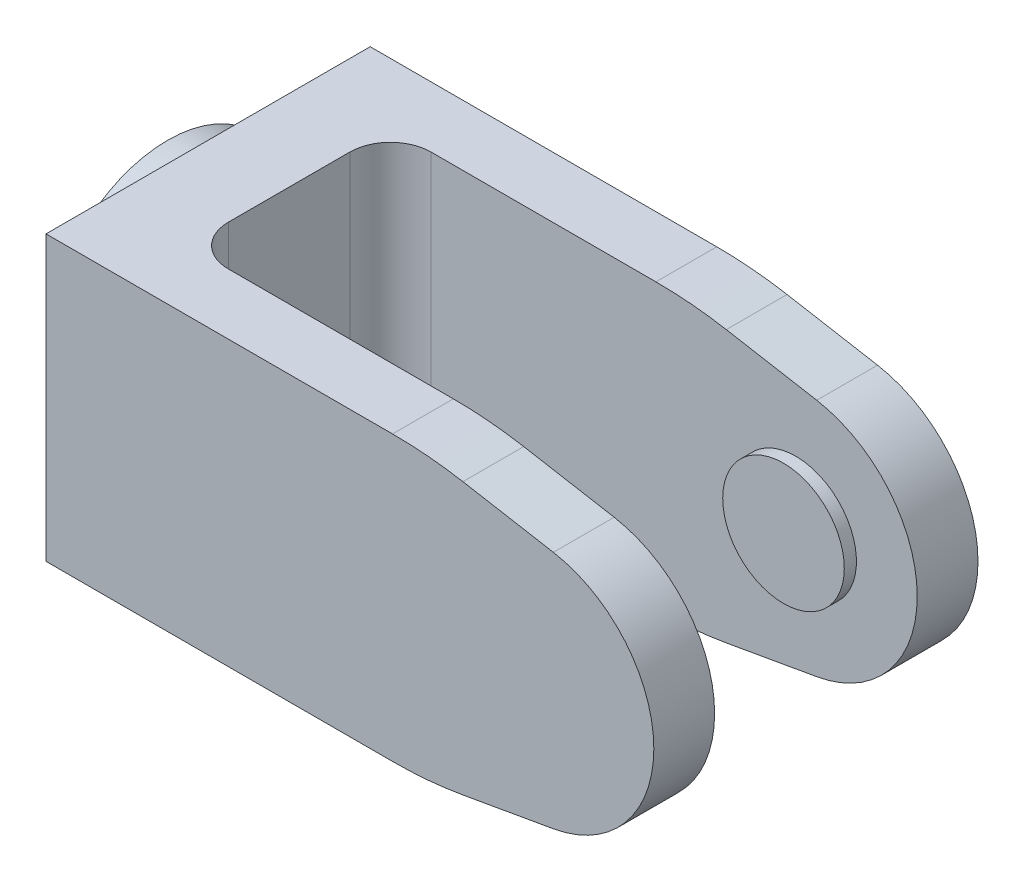
SolidWorks part; units mm, degrees
ref_plane "Front Plane" through (0, 0, 0) normal (0, 0, 1) x (1, 0, 0)
ref_plane "Top Plane" through (0, 0, 0) normal (0, 1, 0) x (1, 0, 0)
ref_plane "Right Plane" through (0, 0, 0) normal (1, 0, 0) x (0, 0, -1)
sketch "Sketch1" plane through (0, 0, 0) normal (0, 0, 1) x (1, 0, 0)
  line L0 (-54.1597, -43.8848) -> (40.1086, -43.8848)
  line L1 (40.1086, -43.8848) -> (71.0498, -38.4291)
  line L2 (71.0498, 20.6594) -> (40.1086, 26.1152)
  line L3 (40.1086, 26.1152) -> (-54.1597, 26.1152)
  line L4 (-54.1597, 26.1152) -> (-54.1597, -43.8848)
  arc A0 (71.0498, -38.4291) -> (71.0498, 20.6594) centre (65.8403, -8.8848) ccw
  dimension "D1" = 170
  dimension "D2" = 170
  dimension "D3" = 70
  dimension "D4" = 120
extrude "Boss-Extrude1" add sketch "Sketch1" along normal mid plane 80
sketch "Sketch2" plane through (0, 0, 0) normal (0, 1, 0) x (1, 0, 0)
  line L0 (40.1086, 40) -> (-54.1597, 40) construction
  line L1 (-34.1597, 25) -> (120.6231, 25)
  line L2 (-34.1597, 25) -> (-34.1597, -25)
  line L3 (-34.1597, -25) -> (120.6231, -25)
  line L4 (120.6231, 25) -> (120.6231, -25)
  line L5 (40.1086, -40) -> (-54.1597, -40) construction
  line L6 (-54.1597, -40) -> (-54.1597, 40) construction
  dimension "D1" = 154.7827
  dimension "D2" = 15
  dimension "D3" = 15
  dimension "D4" = 20
extrude "Cut-Extrude1" cut sketch "Sketch2" against normal through all
extrude "Cut-Extrude2" cut sketch "Sketch2<2>" along normal through all
sketch "Sketch2<2>" plane through (0, 0, 0) normal (0, 1, 0) x (1, 0, 0) same geometry as "Sketch2"
sketch "Sketch3" plane through (0, 0, -25) normal (0, 0, 1) x (1, 0, 0)
  circle A0 centre (65.8403, -8.8848) radius 15
  dimension "D1" = 30
extrude "Boss-Extrude2" add sketch "Sketch3" along normal blind 3
mirror "Mirror1" about plane through (0, 0, 0) normal (0, 0, 1) of "Boss-Extrude2"
sketch "Sketch4" plane through (-54.1597, 0, 0) normal (-1, 0, 0) x (0, 0, 1)
  circle A1 centre (0, -8.8848) radius 30
extrude "Boss-Extrude3" add sketch "Sketch4" along normal blind 10
sketch "Sketch5" plane through (-64.1597, 0, 0) normal (-1, 0, 0) x (0, 0, 1)
  circle A0 centre (0, -8.8848) radius 25
  dimension "D1" = 50
extrude "Boss-Extrude4" add sketch "Sketch5" along normal blind 3
fillet "Fillet1" radius 100 2 edges at (40.1086, 26.1152, 32.5) (40.1086, 26.1152, -32.5)
fillet "Fillet2" radius 100 2 edges at (40.1086, -43.8848, -32.5) (40.1086, -43.8848, 32.5)
fillet "Fillet3" radius 10 2 edges at (-34.1597, -8.8848, 25) (-34.1597, -8.8848, -25)
